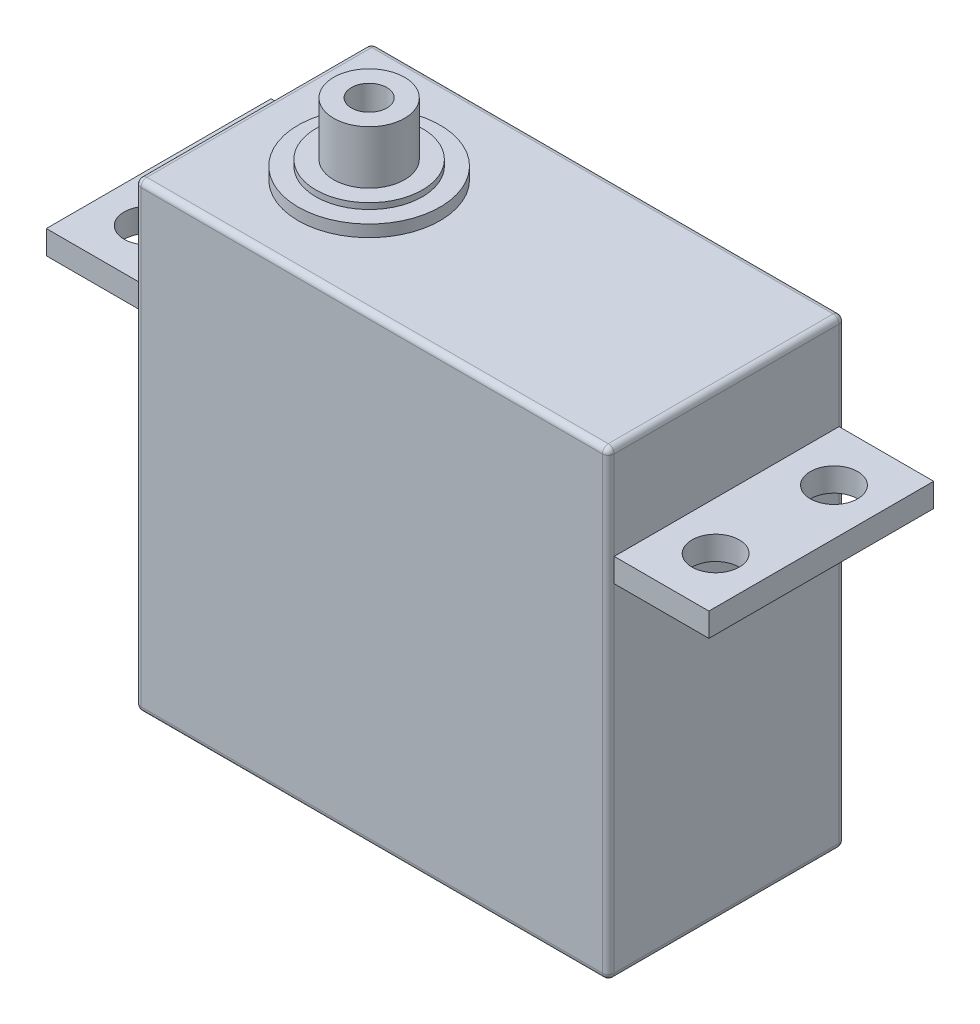
SolidWorks part; units mm, degrees
ref_plane "前视基准面" through (0, 0, 0) normal (0, 0, 1) x (1, 0, 0)
ref_plane "上视基准面" through (0, 0, 0) normal (0, 1, 0) x (1, 0, 0)
ref_plane "右视基准面" through (0, 0, 0) normal (1, 0, 0) x (0, 0, -1)
other "Configuration Table"
sketch "草图1" plane through (0, 0, 0) normal (0, 0, 1) x (1, 0, 0)
  line L1 (0, 0) -> (40, 0)
  line L2 (0, 0) -> (0, 39)
  line L3 (0, 39) -> (40, 39)
  line L4 (40, 0) -> (40, 39)
  dimension "D1" = 40
  dimension "D2" = 39
extrude "凸台-拉伸2" add sketch "草图1" along normal blind 20 contours L3 L4 L1 L2
fillet "圆角2" radius 0.5 2 edges at (40, 19.5, 20) (20, 39, 20)
fillet "圆角3" radius 0.5 6 edges at (40, 0, 9.75) (39.8536, 0, 19.8536) (0, 39, 9.75) (0, 38.8536, 19.8536) (19.75, 0, 20) (0, 19.25, 20)
fillet "圆角4" radius 0.5 5 edges at (39.8536, 38.8536, 19.8536) (19.75, 0, 0) (39.8536, 0.1464, 0) (40, 39, 9.75) (40, 19.75, 0)
fillet "圆角5" radius 0.5 7 edges at (0.1464, 0.1464, 19.8536) (0, 0, 10) (0, 0.1464, 0.1464) (39.8536, 38.8536, 0.1464) (20, 39, 0) (0.1464, 38.8536, 0) (0, 19.5, 0)
sketch "草图6" plane through (0, 0, 0) normal (-1, 0, 0) x (0, 0, 1)
  line L0 (19.5, 0.5) -> (19.5, 38.5) construction
  line L1 (0.5, 38.5) -> (0.5, 0.5) construction
  line L2 (19.5, 31) -> (0.5, 31)
  line L3 (19.5, 31) -> (19.5, 29)
  line L4 (19.5, 29) -> (0.5, 29)
  line L5 (0.5, 31) -> (0.5, 29)
  line L6 (19.5, 0) -> (0.5, 0) construction
  dimension "D1" = 2
  dimension "D2" = 31
extrude "凸台-拉伸3" add sketch "草图6" along normal blind 8
sketch "草图7" plane through (40, 0, 0) normal (1, 0, 0) x (0, 0, -1)
  line L0 (-0.5, 0.5) -> (-0.5, 38.5) construction
  line L1 (-0.5, 31) -> (-19.5, 31)
  line L2 (-0.5, 31) -> (-0.5, 29)
  line L3 (-0.5, 29) -> (-19.5, 29)
  line L4 (-19.5, 31) -> (-19.5, 29)
  line L5 (-19.5, 38.5) -> (-19.5, 0.5) construction
  line L6 (-0.5, 0) -> (-19.5, 0) construction
  dimension "D1" = 2
  dimension "D2" = 31
extrude "凸台-拉伸5" add sketch "草图7" along normal blind 8
sketch "草图8" plane through (0, 39, 0) normal (0, 1, 0) x (1, 0, 0)
  line L1 (-8, -10) -> (48, -10) construction
  line L2 (-8, -19.5) -> (-8, -0.5) construction
  line L3 (48, -0.5) -> (48, -19.5) construction
  circle A0 centre (-3.9282, -5) radius 2
  circle A1 centre (-3.9282, -15) radius 2
  circle A2 centre (44.0718, -5) radius 2
  circle A3 centre (44.0718, -15) radius 2
  point P10 (0, 0)
  point P12 (45.8335, -0.7611)
  dimension "D1" = 4
  dimension "D2" = 4
  dimension "D3" = 4
  dimension "D4" = 4
  dimension "D5" = 10
  dimension "D6" = 10
  dimension "D7" = 48
extrude "切除-拉伸1" cut sketch "草图8" against normal blind 28
sketch "草图9" plane through (0, 39, 0) normal (0, 1, 0) x (1, 0, 0)
  circle A0 centre (10.0718, -10.288) radius 6
  circle A1 centre (10.0718, -10.288) radius 4.5
  circle A2 centre (10.0718, -10.288) radius 3
  point P4 (-3.9282, -5)
  dimension "D1" = 12
  dimension "D2" = 9
  dimension "D3" = 6
  dimension "D4" = 14
extrude "凸台-拉伸7" add sketch "草图9" along normal blind 1 contours A0 A1 region at (4.2416, 39, 10.288)
sketch "草图10" plane through (0, 39, 0) normal (0, 1, 0) x (1, 0, 0)
  circle A0 centre (10.0718, -10.288) radius 4.5
extrude "凸台-拉伸8" add sketch "草图10" along normal blind 1.5
sketch "草图11" plane through (0, 40.5, 0) normal (0, 1, 0) x (1, 0, 0)
  circle A0 centre (10.0718, -10.288) radius 3
  dimension "D1" = 6
extrude "凸台-拉伸9" add sketch "草图11" along normal blind 4.5
sketch "草图12" plane through (0, 45, 0) normal (0, 1, 0) x (1, 0, 0)
  circle A0 centre (10.0718, -10.288) radius 1.5
  dimension "D1" = 3
extrude "切除-拉伸2" cut sketch "草图12" against normal blind 6
